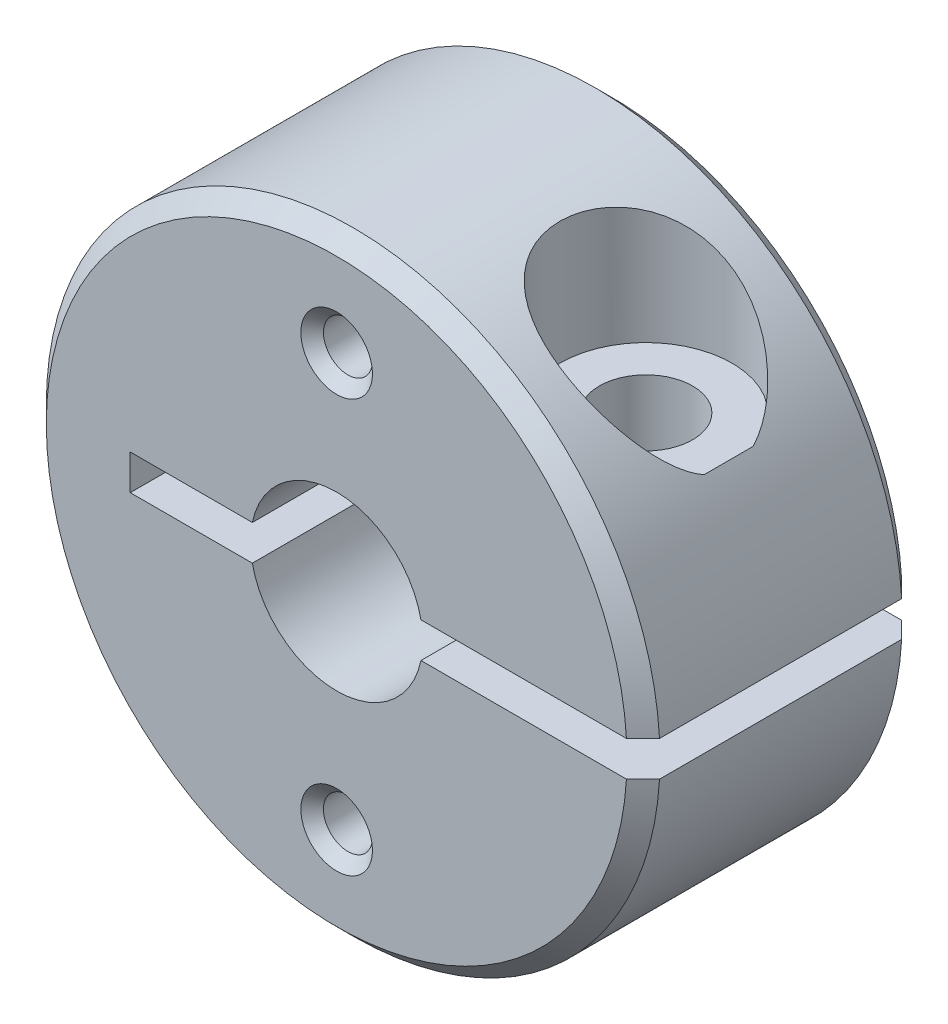
SolidWorks part; units mm, degrees
material "ASTM A36 Steel"
ref_plane "Front Plane" through (0, 0, 0) normal (0, 0, 1) x (1, 0, 0)
ref_plane "Top Plane" through (0, 0, 0) normal (0, 1, 0) x (1, 0, 0)
ref_plane "Right Plane" through (0, 0, 0) normal (1, 0, 0) x (0, 0, -1)
ref_axis "Axis1" through (0, 0, -13.335) along (0, 0, 1)
ref_plane "Plane1" through (0, 0, -6.35) normal (0, 0, 1) x (1, 0, 0)
sketch "Sketch1" plane through (0, 0, 0) normal (1, 0, 0) x (0, 0, -1)
  line L0 (0, 3.9751) -> (11.684, 3.9751)
  line L1 (11.684, 3.9751) -> (11.684, 5.5562)
  line L2 (11.684, 5.5562) -> (12.7, 5.5562)
  line L3 (12.7, 5.5562) -> (12.7, 14.1605)
  line L4 (12.7, 14.1605) -> (0, 14.1605)
  line L5 (0, 14.1605) -> (0, 3.9751)
  line L6 (16.3929, 0) -> (34.5272, 0) construction
  dimension "D1" = 12.7
  dimension "D2" = 1.016
  dimension "D3" = 7.9502
  dimension "D4" = 11.1125
  dimension "D5" = 28.321
revolve "Revolve1" add sketch "Sketch1" angle 360 about L6
chamfer "Chamfer1" distance 0.762 angle 45 2 edges at (14.1605, 0, -12.7) (14.1605, 0, 0)
sketch "Sketch2" plane through (0, 0, -6.35) normal (0, 0, 1) x (1, 0, 0)
  line L0 (10.0774, 0) -> (10.0775, 7.9248)
  line L1 (10.0775, 7.9248) -> (11.8999, 7.9248)
  line L2 (11.8999, 7.9248) -> (11.8999, 20.6248)
  line L3 (11.8999, 20.6248) -> (7.9248, 20.6248)
  line L4 (7.9248, 20.6248) -> (7.9248, -19.869)
  line L5 (7.9248, -19.869) -> (9.652, -18.8718)
  line L6 (9.652, -18.8718) -> (9.652, -0.2456)
  line L7 (9.652, -0.2456) -> (10.0774, 0)
  line L8 (7.9248, -19.869) -> (7.9248, -30.1523) construction
  dimension "D1" = 60
  dimension "D2" = 3.4544
  dimension "D3" = 4.3053
  dimension "D4" = 7.9502
  dimension "D5" = 7.9248
  dimension "D6" = 7.9248
  dimension "D7" = 12.7
revolve "Cut-Revolve1" cut sketch "Sketch2" angle 360 about L8
hole_wizard "#4-40 Tapped Hole1" positions "Sketch6" profile "Sketch5" tap size "#4-40" standard "ANSI Inch" end condition through all
sketch "Sketch6" plane through (0, 0, -12.7) normal (0, 0, -1) x (-1, 0, 0)
  point P0 (0, 9.525)
  point P2 (0, -9.525)
  dimension "D1" = 9.525
  dimension "D2" = 9.525
sketch "Sketch5" plane through (0, 9.525, -12.7) normal (1, 0, 0) x (0, 1, 0)
  line L0 (0, 0) -> (0, 12.7)
  line L1 (0, 12.7) -> (1.651, 12.7)
  line L2 (1.1303, 12.1793) -> (1.1303, 0.5207)
  line L3 (1.1303, 0.5207) -> (1.651, 0)
  line L5 (1.651, 0) -> (0, 0)
  line L6 (-1.1303, 0.5207) -> (-1.651, 0) construction
  line L7 (1.651, 12.7) -> (1.1303, 12.1793)
  line L8 (-1.651, 12.7) -> (-1.1303, 12.1793) construction
  line L11 (0, -6.35) -> (0, 107.95) construction
  dimension "Thru Tap Drill Dia." = 2.2606
  dimension "Thru Tap Drill Depth" = 12.7
  dimension "Near C'Sink Dia." = 3.302
  dimension "Near C'Sink Angle" = 90
  dimension "Far C'Sink Dia." = 3.302
  dimension "Far C'Sink Angle" = 90
cosmetic thread "Hole Thread3" parameters "D2"=2.8448
cosmetic thread "Hole Thread4" parameters "D2"=2.8448
sketch "Sketch4" plane through (0, 0, 0) normal (0, 1, 0) x (1, 0, 0)
  line L1 (-9.525, 35.5874) -> (25.4, 35.5874)
  line L2 (-9.525, 35.5874) -> (-9.525, -6.8084)
  line L3 (-9.525, -6.8084) -> (25.4, -6.8084)
  line L4 (25.4, 35.5874) -> (25.4, -6.8084)
  dimension "D1" = 9.525
  dimension "D2" = 25.4
extrude "Cut-Extrude1" cut sketch "Sketch4" against normal mid plane 1.6256
ref_axis "Axis2" [suppressed] through (0, -20.6565, 0) along (0, 1, 0)
pattern_linear "LPattern1" [suppressed] count 2 spacing 101.6 along (0, 1, 0) of bodies 108
sketch "Sketch7" [suppressed] plane through (0, 0, -12.7) normal (0, 0, -1) x (-1, 0, 0)
  circle A0 centre (0, 0) radius 14.1605
  circle A1 centre (0, 101.6) radius 14.1605
  circle A2 centre (0, 0) radius 14.1605 construction
